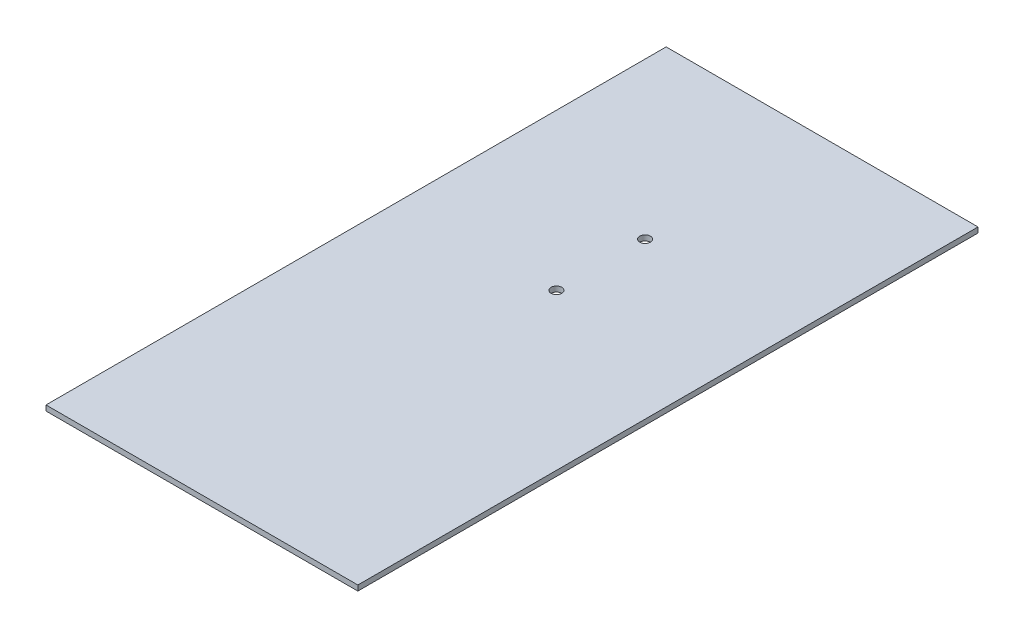
SolidWorks part; units mm, degrees
ref_plane "Front Plane" through (0, 0, 0) normal (0, 0, 1) x (1, 0, 0)
ref_plane "Top Plane" through (0, 0, 0) normal (0, 1, 0) x (1, 0, 0)
ref_plane "Right Plane" through (0, 0, 0) normal (1, 0, 0) x (0, 0, -1)
sketch "Sketch1" plane through (0, 0, 0) normal (0, 1, 0) x (1, 0, 0)
  line L1 (0, 0) -> (176, 0)
  line L2 (0, 0) -> (0, 350)
  line L3 (0, 350) -> (176, 350)
  line L4 (176, 0) -> (176, 350)
  dimension "D1" = 350
  dimension "D2" = 176
extrude "Boss-Extrude1" add sketch "Sketch1" along normal blind 3
hole_wizard "Ø6.0mm Dowel Hole1" positions "Sketch2" profile "Sketch3" hole size "Ø6.0" standard "ANSI Metric" end condition up to next
sketch "Sketch2" plane through (0, 0, 0) normal (0, -1, 0) x (-1, 0, 0)
  point P0 (-88.0169, 250.06)
  point P3 (-88.0169, 200.06)
sketch "Sketch3" plane through (88.0169, 0, -250.06) normal (1, 0, 0) x (0, 0, -1)
  line L0 (0, 0) -> (0, 3)
  line L1 (0, 3) -> (3, 3)
  line L2 (3, 3) -> (3, 0)
  line L5 (3, 0) -> (0, 0)
  line L11 (0, -6.35) -> (0, 107.95) construction
  dimension "Thru Hole Dia." = 6
  dimension "Thru Hole Depth" = 3
